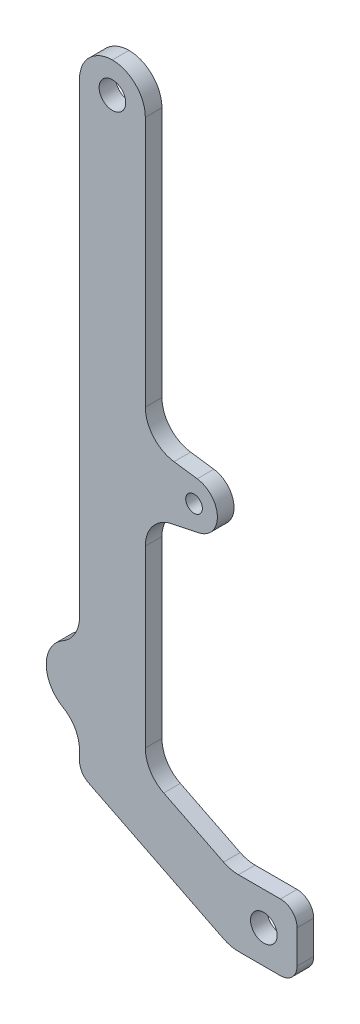
SolidWorks part; units mm, degrees
ref_plane "Front Plane" through (0, 0, 0) normal (0, 0, 1) x (1, 0, 0)
ref_plane "Top Plane" through (0, 0, 0) normal (0, 1, 0) x (1, 0, 0)
ref_plane "Right Plane" through (0, 0, 0) normal (1, 0, 0) x (0, 0, -1)
sketch "Sketch1" plane through (0, 0, 0) normal (0, 0, 1) x (1, 0, 0)
  line L0 (-10, 10) -> (10, 10)
  line L1 (10, 10) -> (10, -10)
  line L2 (10, -10) -> (-10, -10)
  line L12 (0, 0) -> (67.8578, 0) construction
  line L13 (-85.9774, 80) -> (-110, 80) construction
  line L14 (-100, 172.9697) -> (-100, 80) construction
  line L17 (0, 0) -> (0, 249.807) construction
  line L18 (-92.1407, 77.1927) -> (-83.9804, 80.9048) construction
  line L19 (-83.0728, 52.7744) -> (-72.0556, 62.9902) construction
  line L20 (0, 0) -> (-39.6944, 40.4963) construction
  line L24 (-79.9152, 86.788) -> (-79.467, 70.983) construction
  line L33 (-79.467, 70.983) -> (-69.6254, 58.6079) construction
  line L45 (-69.6254, 58.6079) -> (-79.9152, 86.788) construction
  line L51 (-11, 115) -> (-11, 85) construction
  line L56 (-11, 115) -> (-21, 100) construction
  line L57 (82.8895, 212.3203) -> (5.5915, 72.231) construction
  line L58 (-30, 20) -> (30, 20) construction
  line L59 (-30, 20) -> (-30, 180) construction
  line L60 (-30, 180) -> (30, 180) construction
  line L61 (30, 20) -> (30, 180) construction
  line L62 (-30, 20) -> (30, 180) construction
  line L63 (-30, 180) -> (30, 20) construction
  line L68 (82.8895, 212.3203) -> (135.423, 183.3336) construction
  line L69 (5.5915, 72.231) -> (58.125, 43.2443) construction
  line L70 (135.423, 183.3336) -> (58.125, 43.2443) construction
  line L71 (109.1562, 197.827) -> (31.8583, 57.7376) construction
  line L72 (-98.7689, 157.7553) -> (42.1544, 203.3398) construction
  line L77 (-21, 100) -> (-11, 85) construction
  line L78 (-11, 100) -> (-21, 100) construction
  line L79 (-19.5557, 93.1223) -> (-35.6529, 89.7418)
  line L80 (-35.6529, 89.7418) -> (-35.6529, 22.8264)
  line L81 (-10, 10) -> (-35.6529, 22.8264)
  line L82 (-20.0379, 106.9616) -> (-35.6529, 109.1196)
  line L83 (-35.6529, 109.1196) -> (-35.6529, 203.3398)
  line L84 (0, 0) -> (-55.461, 264.1001) construction
  line L85 (-10, -10) -> (-55.461, 12.7305)
  line L86 (-45.557, 203.3398) -> (-45.557, 167.2664) construction
  line L87 (-35.6529, 203.3398) -> (-55.461, 203.3398)
  line L88 (-55.461, 203.3398) -> (-55.461, 45.906)
  line L89 (-332.8823, 14.578) -> (-312.8823, 14.578) construction
  line L90 (-312.8823, 14.578) -> (-312.8823, -5.422) construction
  line L91 (-312.8823, -5.422) -> (-332.8823, -5.422) construction
  line L92 (-342.4379, 97.7003) -> (-358.5352, 94.3199) construction
  line L93 (-358.5352, 94.3199) -> (-358.5352, 27.4044) construction
  line L94 (-332.8823, 14.578) -> (-358.5352, 27.4044) construction
  line L95 (-342.9201, 111.5396) -> (-358.5352, 113.6977) construction
  line L96 (-358.5352, 113.6977) -> (-358.5352, 207.9178) construction
  line L97 (-332.8823, -5.422) -> (-378.3433, 17.3085) construction
  line L98 (-358.5352, 207.9178) -> (-378.3433, 207.9178) construction
  line L99 (-378.3433, 207.9178) -> (-378.3433, 17.3085) construction
  line L100 (-55.461, 25.906) -> (-55.461, 12.7305)
  circle A0 centre (0, 0) radius 4
  arc A3 (-93.1578, 80) -> (41.9046, 115.4226) centre (0, 0) cw construction
  arc A10 (-10, 10) -> (-83.0728, 52.7744) centre (-10, 93.8033) ccw construction
  circle A13 centre (-79.9152, 86.788) radius 11 construction
  circle A14 centre (-69.6254, 58.6079) radius 11 construction
  arc A15 (-64.4376, 76.4709) -> (0, 100) centre (0, 0) cw construction
  circle A16 centre (0, 100) radius 70 construction
  circle A17 centre (-79.467, 70.983) radius 5 construction
  arc A18 (-83.9804, 80.9048) -> (-72.0556, 62.9902) centre (-79.467, 70.983) cw construction
  arc A20 (-100, 156.8374) -> (0, 186.0053) centre (0, 0) cw construction
  circle A21 centre (40, 210) radius 7 construction
  arc A22 (-342.4379, 97.7003) -> (-342.9201, 111.5396) centre (-343.8823, 104.578) ccw construction
  circle A24 centre (-11, 115) radius 11 construction
  circle A25 centre (-11, 85) radius 11 construction
  circle A26 centre (-21, 100) radius 2.5
  arc A27 (-19.5557, 93.1223) -> (-20.0379, 106.9616) centre (-21, 100) ccw
  circle A29 centre (-45.557, 194.1725) radius 4
  arc A30 (-55.461, 45.906) -> (-55.461, 25.906) centre (-55.461, 35.906) ccw
  point P63 (-63.5329, 77.2241)
  point P84 (-322.8823, 4.578)
  dimension "D1" = 8
  dimension "D13" = 19.8081
  dimension "D7" = 60
  dimension "D27" = 22
  dimension "D22" = 100
  dimension "D23" = 140
  dimension "D16" = 14
  dimension "D12" = 22
  dimension "D18" = 5
  dimension "D19" = 190.6093
  dimension "D32" = 7.0278
  dimension "D2" = 10
  dimension "D3" = 10
  dimension "D4" = 10
  dimension "D5" = 93.1578
  dimension "D6" = 100
  dimension "D8" = 20
  dimension "D9" = 80
  dimension "D10" = 40
  dimension "D11" = 80
  dimension "D14" = 30
  dimension "D15" = 210
  dimension "D17" = 10
  dimension "D20" = 45.461
  dimension "D21" = 22.7305
  dimension "D24" = 20
  dimension "D25" = 30
  dimension "D26" = 20
  dimension "D28" = 20
  dimension "D29" = 28.6808
  dimension "D30" = 66.9154
  dimension "D31" = 94.2201
  dimension "D33" = 97.869
  dimension "D34" = 101.86
  dimension "D35" = 153.435
  dimension "D36" = 153.435
  dimension "D37" = 116.565
  dimension "D38" = 10
  dimension "D39" = 10
extrude "Boss-Extrude1" add sketch "Sketch1" along normal blind 5
fillet "Fillet3" radius 5 2 edges at (10, -10, 2.5) (10, 10, 2.5)
fillet "Fillet4" radius 10 9 edges at (-55.461, 203.3398, 2.5) (-35.6529, 203.3398, 2.5) (-35.6529, 89.7418, 2.5) (-10, -10, 2.5) (-10, 10, 2.5) (-35.6529, 22.8264, 2.5) (-35.6529, 109.1196, 2.5) (-55.461, 25.906, 2.5) (-55.461, 45.906, 2.5)
fillet "Fillet5" radius 5 1 edges at (-55.461, 12.7305, 2.5)
